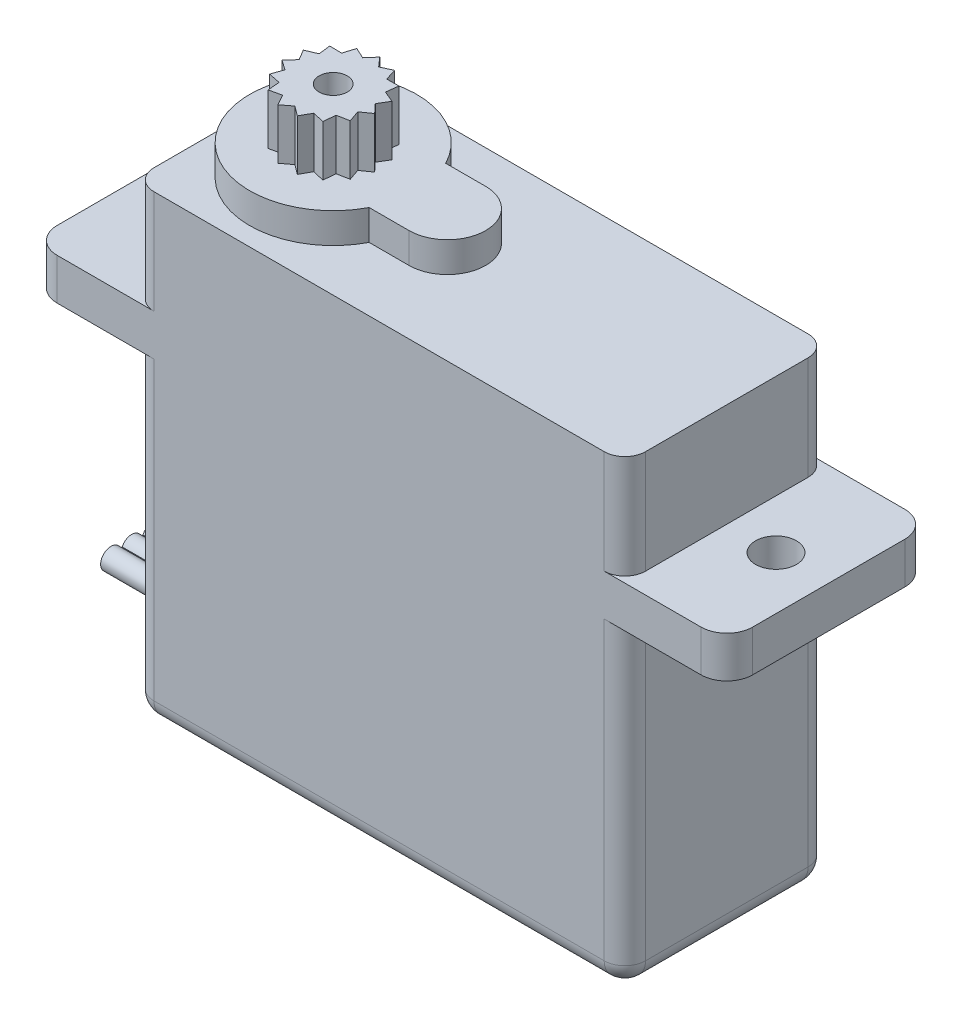
SolidWorks part; units mm, degrees
material "Plain Carbon Steel"
ref_plane "Front Plane" through (0, 0, 0) normal (0, 0, 1) x (1, 0, 0)
ref_plane "Top Plane" through (0, 0, 0) normal (0, 1, 0) x (1, 0, 0)
ref_plane "Right Plane" through (0, 0, 0) normal (1, 0, 0) x (0, 0, -1)
sketch "Sketch1" plane through (0, 0, 0) normal (0, 0, 1) x (1, 0, 0)
  line L0 (0, 0) -> (0, 15.3)
  line L1 (0, 22.3) -> (23.75, 22.3)
  line L2 (23.75, 15.3) -> (23.75, 0)
  line L3 (23.75, 0) -> (0, 0)
  line L5 (23.75, 15.3) -> (28.675, 15.3)
  line L6 (28.675, 15.3) -> (28.675, 17.3)
  line L7 (28.675, 17.3) -> (23.75, 17.3)
  line L8 (-4.925, 17.3) -> (-4.925, 15.3)
  line L9 (-4.925, 15.3) -> (0, 15.3)
  line L11 (23.75, 22.3) -> (23.75, 17.3)
  line L12 (0, 17.3) -> (0, 22.3)
  line L19 (0, 17.3) -> (-4.925, 17.3)
  dimension "D1" = 15.3
  dimension "D2" = 23.75
  dimension "D3" = 7
  dimension "D4" = 33.6
  dimension "D5" = 2
extrude "Boss-Extrude1" add sketch "Sketch1" along normal mid plane 9.85
sketch "Sketch5" plane through (0, 22.3, 0) normal (0, 1, 0) x (1, 0, 0)
  line L0 (0, -4.925) -> (0, 4.925) construction
  line L1 (23.75, 4.925) -> (0, 4.925) construction
  line L2 (4.735, 0) -> (11.875, 0) construction
  line L6 (10.25, 1.85) -> (8.3209, 1.85)
  line L7 (10.25, -1.85) -> (8.3209, -1.85)
  arc A0 (8.3209, 1.85) -> (8.3209, -1.85) centre (4.735, 0) ccw
  arc A1 (10.25, 1.85) -> (10.25, -1.85) centre (10.25, 0) cw
  point P1 (0.7, 0)
  point P6 (11.875, 4.925)
  point P18 (12.1, 0)
  dimension "D1" = 8.07
  dimension "D2" = 0.7
  dimension "D3" = 7.14
  dimension "D4" = 3.7
  dimension "D5" = 11.4
extrude "Boss-Extrude3" add sketch "Sketch5" along normal blind 1.46
sketch "Sketch6" plane through (0, 23.76, 0) normal (0, 1, 0) x (1, 0, 0)
  line L0 (4.3504, 1.8096) -> (4.735, 2.25)
  line L1 (4.735, 0) -> (4.3504, 1.8096) construction
  line L2 (4.735, 0) -> (5.1196, 1.8096) construction
  line L3 (5.1196, 1.8096) -> (4.3504, 1.8096) construction
  line L4 (4.735, 2.25) -> (5.1196, 1.8096)
  line L5 (5.1196, 1.8096) -> (5.6502, 2.0555)
  line L6 (5.6502, 2.0555) -> (5.8224, 1.4967)
  line L7 (5.8224, 1.4967) -> (6.4071, 1.5055)
  line L8 (6.4071, 1.5055) -> (6.3371, 0.925)
  line L9 (6.3371, 0.925) -> (6.8749, 0.6953)
  line L10 (6.8749, 0.6953) -> (6.5749, 0.1934)
  line L11 (6.5749, 0.1934) -> (6.9727, -0.2352)
  line L12 (6.9727, -0.2352) -> (6.4945, -0.5717)
  line L13 (6.4945, -0.5717) -> (6.6836, -1.125)
  line L14 (6.6836, -1.125) -> (6.1098, -1.2379)
  line L15 (6.1098, -1.2379) -> (6.0575, -1.8203)
  line L16 (6.0575, -1.8203) -> (5.4875, -1.6901)
  line L17 (5.4875, -1.6901) -> (5.2028, -2.2008)
  line L18 (5.2028, -2.2008) -> (4.735, -1.85)
  line L19 (4.735, -1.85) -> (4.2672, -2.2008)
  line L20 (4.2672, -2.2008) -> (3.9825, -1.6901)
  line L21 (3.9825, -1.6901) -> (3.4125, -1.8203)
  line L22 (3.4125, -1.8203) -> (3.3602, -1.2379)
  line L23 (3.3602, -1.2379) -> (2.7864, -1.125)
  line L24 (2.7864, -1.125) -> (2.9755, -0.5717)
  line L25 (2.9755, -0.5717) -> (2.4973, -0.2352)
  line L26 (2.4973, -0.2352) -> (2.8951, 0.1934)
  line L27 (2.8951, 0.1934) -> (2.5951, 0.6953)
  line L28 (2.5951, 0.6953) -> (3.1329, 0.925)
  line L29 (3.1329, 0.925) -> (3.0629, 1.5055)
  line L30 (3.0629, 1.5055) -> (3.6476, 1.4967)
  line L31 (3.6476, 1.4967) -> (3.8198, 2.0555)
  line L32 (3.8198, 2.0555) -> (4.3504, 1.8096)
  circle A0 centre (4.735, 0) radius 2.25 construction
  circle A1 centre (4.735, 0) radius 0.68
  circle A2 centre (4.735, 0) radius 1.85 construction
  point P6 (4.735, 1.8096)
  point P53 (4.735, 0)
  dimension "D1" = 4.5
  dimension "D2" = 1.36
  dimension "D3" = 3.7
  dimension "D4" = 24
  dimension "D5" = 15
extrude "Boss-Extrude4" add sketch "Sketch6" along normal blind 2.45
sketch "Sketch2" plane through (0, 17.3, 0) normal (0, 1, 0) x (1, 0, 0)
  line L0 (-4.925, 0) -> (-2.375, 0) construction
  line L1 (-4.925, -4.925) -> (-4.925, 4.925) construction
  line L2 (26.125, 0) -> (28.675, 0) construction
  line L3 (28.675, -4.925) -> (28.675, 4.925) construction
  circle A0 centre (-2.375, 0) radius 0.99
  circle A1 centre (26.125, 0) radius 0.99
  dimension "D2" = 28.5
  dimension "D1" = 1.98
extrude "Cut-Extrude6" cut sketch "Sketch2" against normal blind 10 contours A1 | A0 region at (26.125, 17.3, 0)
fillet "Fillet1" radius 1 12 edges at (0, 0, 0) (11.875, 0, 4.925) (23.75, 0, 0) (11.875, 0, -4.925) (0, 7.65, -4.925) (0, 19.8, -4.925) (0, 7.65, 4.925) (0, 19.8, 4.925) (23.75, 19.8, 4.925) (23.75, 19.8, -4.925) (23.75, 7.65, -4.925) (23.75, 7.65, 4.925)
fillet "Fillet2" radius 1.25 4 edges at (28.675, 16.3, -4.925) (-4.925, 16.3, -4.925) (-4.925, 16.3, 4.925) (28.675, 16.3, 4.925)
sketch "Sketch7" plane through (0, 0, 0) normal (-1, 0, 0) x (0, 0, 1)
  line L0 (-0.5437, 2.2043) -> (-0.4563, 2.2043)
  line L1 (0.4563, 2.2043) -> (0.5437, 2.2043)
  line L2 (0.5437, 1.7957) -> (0.4563, 1.7957)
  line L3 (-0.4563, 1.7957) -> (-0.5437, 1.7957)
  arc A0 (0.4563, 2.2043) -> (-0.4563, 2.2043) centre (0, 2) ccw
  arc A1 (0.5437, 1.7957) -> (0.5437, 2.2043) centre (1, 2) ccw
  arc A2 (-0.5437, 2.2043) -> (-0.5437, 1.7957) centre (-1, 2) ccw
  arc A3 (-0.4563, 1.7957) -> (0.4563, 1.7957) centre (0, 2) ccw
  dimension "D1" = 1
  dimension "D2" = 2
extrude "Boss-Extrude5" add sketch "Sketch7" along normal blind 5
ref_axis "Axis1" through (4.735, 26.21, 0) along (0, -1, 0)
